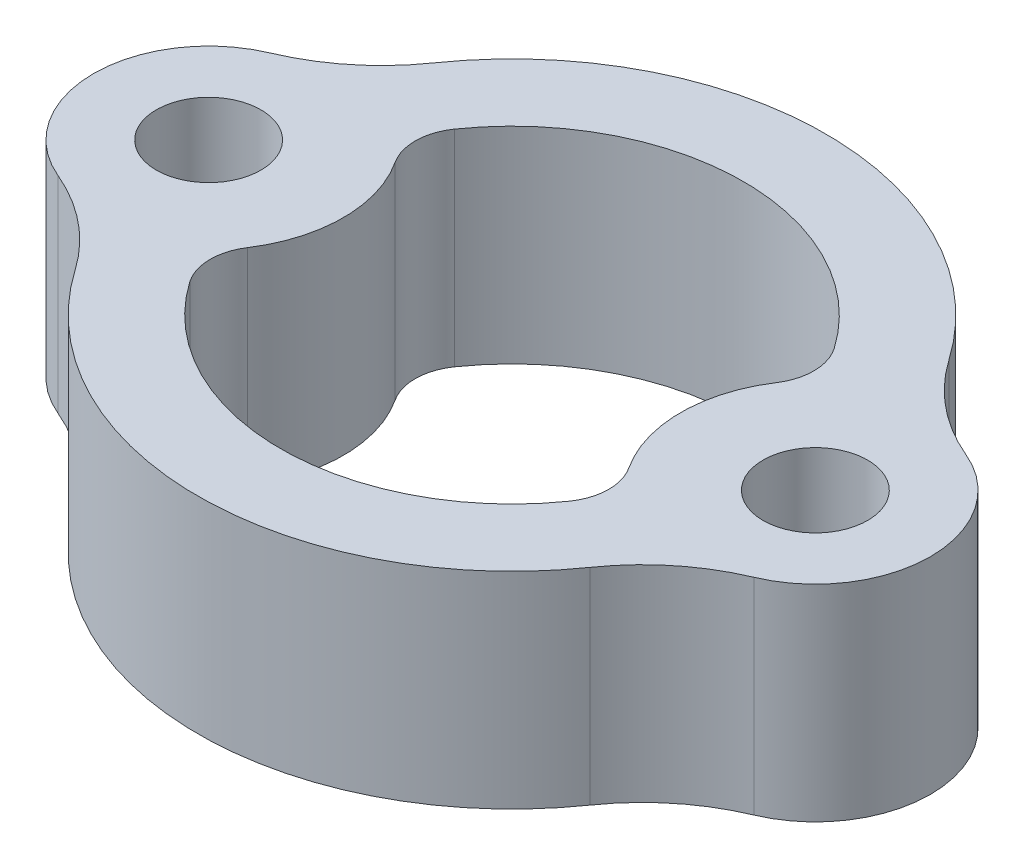
SolidWorks part; units mm, degrees
material "ABS"
ref_plane "Front" through (0, 0, 0) normal (0, 0, 1) x (1, 0, 0)
ref_plane "Top" through (0, 0, 0) normal (0, 1, 0) x (1, 0, 0)
ref_plane "Right" through (0, 0, 0) normal (1, 0, 0) x (0, 0, -1)
ref_axis "X" through (-80.9, 0, 0) along (1, 0, 0)
ref_axis "Y" through (0, -50, 0) along (0, 1, 0)
ref_axis "Z" through (0, 0, -80.9) along (0, 0, 1)
sketch "Sketch1" plane through (0, 0, 0) normal (0, 1, 0) x (1, 0, 0)
  line L0 (-7.366, 0) -> (7.366, 0) construction
  arc A0 (7.0945, 2.7808) -> (-7.0945, 2.7808) centre (0, 0) ccw
  arc A1 (-7.0945, 2.7808) -> (-7.0945, -2.7808) centre (-7.366, 0) ccw
  arc A2 (7.0945, -2.7808) -> (7.0945, 2.7808) centre (7.366, 0) ccw
  arc A3 (-7.0945, -2.7808) -> (7.0945, -2.7808) centre (0, 0) ccw
  circle A4 centre (7.366, 0) radius 1.27
  circle A5 centre (-7.366, 0) radius 1.27
  dimension "D2" = 5.588
  dimension "D3" = 15.24
  dimension "D4" = 2.54
  dimension "D1" = 14.732
extrude "Boss-Extrude1" add sketch "Sketch1" along normal mid plane 5
fillet "Fillet1" radius 5.08 4 edges at (7.0945, 0, -2.7808) (-7.0945, 0, -2.7808) (-7.0945, 0, 2.7808) (7.0945, 0, 2.7808)
sketch "Sketch2" plane through (0, 2.5, 0) normal (0, 1, 0) x (1, 0, 0)
  circle A10 centre (7.366, 0) radius 3.27
  arc A11 (5.2135, 2.4616) -> (5.2135, -2.4616) centre (7.366, 0) ccw
  circle A13 centre (-7.366, 0) radius 3.27
  arc A14 (-5.2135, -2.4616) -> (-5.2135, 2.4616) centre (-7.366, 0) ccw
  arc A16 (-7.6742, 0.7317) -> (-7.6742, -0.7317) centre (-7.366, 0) ccw
  arc A17 (-4.6123, -3.2111) -> (-7.6742, -0.7317) centre (-10.4228, -7.2565) ccw
  arc A18 (-4.6123, -3.2111) -> (4.6123, -3.2111) centre (0, 0) ccw
  arc A19 (7.6742, -0.7317) -> (4.6123, -3.2111) centre (10.4228, -7.2565) ccw
  arc A20 (7.6742, -0.7317) -> (7.6742, 0.7317) centre (7.366, 0) ccw
  arc A21 (4.6123, 3.2111) -> (7.6742, 0.7317) centre (10.4228, 7.2565) ccw
  arc A22 (4.6123, 3.2111) -> (-4.6123, 3.2111) centre (0, 0) ccw
  arc A23 (-7.6742, 0.7317) -> (-4.6123, 3.2111) centre (-10.4228, 7.2565) ccw
  arc A25 (-4.6123, -3.2111) -> (-5.2135, -2.4616) centre (-10.4228, -7.2565) ccw
  arc A26 (-4.6123, -3.2111) -> (4.6123, -3.2111) centre (0, 0) ccw
  arc A27 (5.2135, -2.4616) -> (4.6123, -3.2111) centre (10.4228, -7.2565) ccw
  arc A29 (4.6123, 3.2111) -> (5.2135, 2.4616) centre (10.4228, 7.2565) ccw
  arc A30 (4.6123, 3.2111) -> (-4.6123, 3.2111) centre (0, 0) ccw
  arc A31 (-5.2135, 2.4616) -> (-4.6123, 3.2111) centre (-10.4228, 7.2565) ccw
  dimension "D1" = 2
  dimension "D2" = 2
  dimension "D3" = 2
extrude "Cut-Extrude1" cut sketch "Sketch2" against normal through all
fillet "Fillet2" radius 1.27 4 edges at (5.2135, 0, -2.4616) (-5.2135, 0, -2.4616) (-5.2135, 0, 2.4616) (5.2135, 0, 2.4616)
